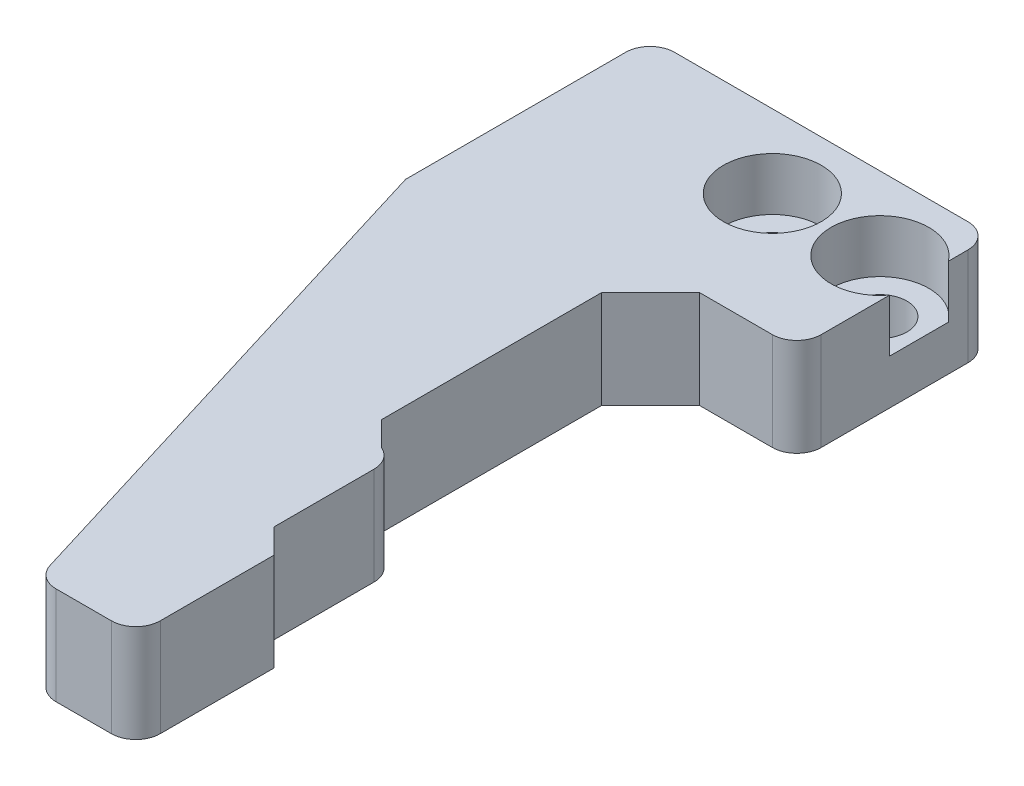
SolidWorks part; units mm, degrees
ref_plane "Front Plane" through (0, 0, 0) normal (0, 0, 1) x (1, 0, 0)
ref_plane "Top Plane" through (0, 0, 0) normal (0, 1, 0) x (1, 0, 0)
ref_plane "Right Plane" through (0, 0, 0) normal (1, 0, 0) x (0, 0, -1)
sketch "Sketch1" plane through (0, 0, 0) normal (0, 1, 0) x (1, 0, 0)
  line L0 (-100, 0) -> (100, 0) construction
  line L1 (0, -100) -> (0, 100) construction
  line L3 (8.5, 4.9075) -> (8.5, 14.7224) construction
  line L4 (8.5, 14.7224) -> (0, 19.6299) construction
  line L5 (0, 19.6299) -> (-8.5, 14.7224) construction
  line L6 (-8.5, 14.7224) -> (-8.5, 4.9075) construction
  line L7 (-8.5, 4.9075) -> (0, 0) construction
  line L8 (0, 0) -> (8.5, 4.9075) construction
  line L9 (11, 17.4641) -> (11, 30.1658) construction
  line L10 (11, 30.1658) -> (0, 36.5167) construction
  line L11 (0, 36.5167) -> (-11, 30.1658) construction
  line L12 (-11, 30.1658) -> (-11, 17.4641) construction
  line L13 (-11, 17.4641) -> (0, 11.1132) construction
  line L14 (0, 11.1132) -> (11, 17.4641) construction
  line L15 (15, 50.4752) -> (0, 59.1355) construction
  line L16 (0, 59.1355) -> (-15, 50.4752) construction
  line L17 (-15, 50.4752) -> (-15, 33.1547) construction
  line L18 (-15, 33.1547) -> (0, 24.4944) construction
  line L19 (0, 24.4944) -> (15, 33.1547) construction
  line L20 (15, 33.1547) -> (15, 50.4752) construction
  circle A0 centre (0, 9.815) radius 8.5 construction
  circle A1 centre (0, 23.815) radius 11 construction
  circle A2 centre (0, 41.815) radius 15 construction
  point P4 (0, 0)
  point P8 (0, 0)
  dimension "D2" = 17
  dimension "D4" = 22
  dimension "D6" = 30
  dimension "D1" = 200
  dimension "D3" = 14
  dimension "D5" = 18
sketch "Sketch2" plane through (0, 0, 0) normal (0, 1, 0) x (1, 0, 0)
  line L0 (0, 59.1355) -> (-14.95, 59.1355)
  line L1 (-14.95, 59.1355) -> (-14.95, 29.1355)
  line L2 (-14.95, 29.1355) -> (-10.95, 29.1355)
  line L3 (-10.95, 29.1355) -> (-10.95, 14.1355)
  line L4 (-10.95, 14.1355) -> (-8.45, 14.1355)
  line L5 (-8.45, 14.1355) -> (-8.45, 0)
  line L6 (-100, 0) -> (100, 0) construction
  line L7 (0, -100) -> (0, 100) construction
  line L8 (0, 59.1355) -> (0, 79.1355)
  line L9 (0, 79.1355) -> (-35, 79.1355)
  line L12 (-8.45, 0) -> (-18.45, 0)
  line L13 (-18.45, 0) -> (-35, 54.1355)
  line L14 (-35, 54.1355) -> (-35, 79.1355)
  dimension "D1" = 14.95
  dimension "D2" = 4
  dimension "D3" = 8.45
  dimension "D4" = 30
  dimension "D5" = 15
  dimension "D6" = 20
  dimension "D7" = 10
  dimension "D8" = 25
  dimension "D9" = 35
extrude "Boss-Extrude1" add sketch "Sketch2" along normal blind 10
chamfer "Chamfer1" distance 5 angle 45 1 edges at (-14.95, 5, -59.1355)
chamfer "Chamfer2" distance 2.5 angle 45 2 edges at (-10.95, 5, -14.1355) (-14.95, 5, -29.1355)
fillet "Fillet1" radius 2.5 6 edges at (0, 5, -79.1355) (-8.45, 5, 0) (-18.45, 5, 0) (-35, 5, -79.1355) (0, 5, -59.1355) (-10.95, 5, -29.1355)
sketch "Sketch3" plane through (0, 10, 0) normal (0, 1, 0) x (1, 0, 0)
  line L0 (-15, 71.6355) -> (-4, 71.6355) construction
  line L1 (-2.5, 79.1355) -> (-32.5, 79.1355) construction
  line L2 (0, -100) -> (0, 100) construction
  dimension "D1" = 11
  dimension "D2" = 7.5
  dimension "D3" = 4
hole_wizard "CBORE for M5 Hex Socket Head Cap Screw2" positions "Sketch6" profile "Sketch7" counterbore size "M5" standard "DIN"
sketch "Sketch6" plane through (0, 10, 0) normal (0, 1, 0) x (1, 0, 0)
  point P0 (-15, 71.6355)
  point P3 (-4, 71.6355)
sketch "Sketch7" plane through (-15, 10, -71.6355) normal (1, 0, 0) x (0, 0, 1)
  line L0 (0, 0) -> (0, 11.6524)
  line L1 (0, 11.6524) -> (2.75, 10)
  line L2 (2.75, 10) -> (2.75, 5.4)
  line L3 (2.75, 5.4) -> (5, 5.4)
  line L4 (5, 5.4) -> (5, 0)
  line L5 (5, 0) -> (0, 0)
  line L10 (0, 11.6524) -> (-2.75, 10) construction
  line L11 (0, -6.35) -> (0, 107.95) construction
  dimension "Hole Dia." = 5.5
  dimension "Hole Depth" = 10
  dimension "C'Bore Dia." = 10
  dimension "C'Bore Depth" = 5.4
  dimension "Drill Angle" = 118
